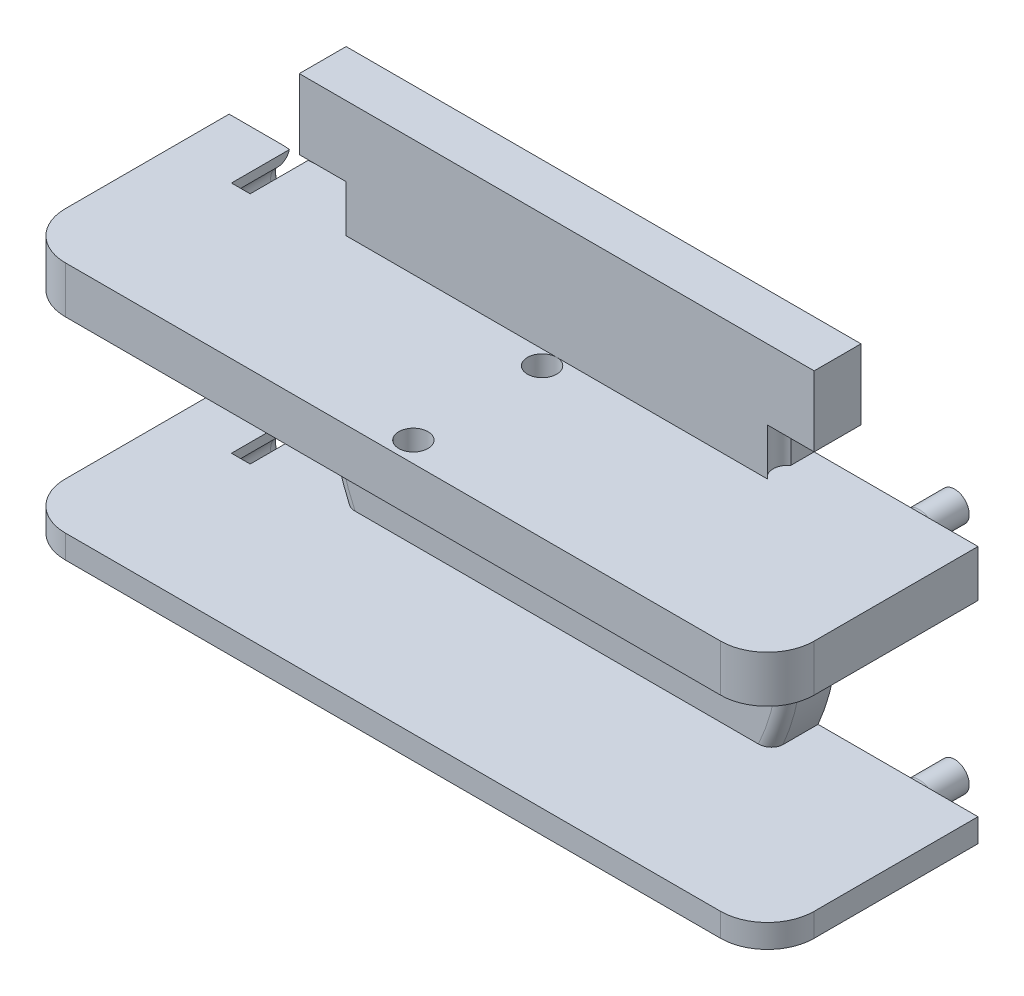
SolidWorks part; units mm, degrees
material "UNOBTANIUM"
ref_plane "Top Plane" through (0, 0, 0) normal (0, 0, 1) x (1, 0, 0)
ref_plane "Right Plane" through (0, 0, 0) normal (0, 1, 0) x (1, 0, 0)
ref_plane "Front Plane" through (0, 0, 0) normal (1, 0, 0) x (0, 0, -1)
ref_axis "x-axis" through (-17.6, 0, 0) along (1, 0, 0)
ref_axis "y-axis" through (0, -9.7375, 0) along (0, 1, 0)
ref_axis "z-axis" through (0, 0, 8.775) along (0, 0, -1)
sketch "Sketch1" plane through (0, 0, 0) normal (0, 0, 1) x (1, 0, 0)
  line L0 (-11, 6) -> (-11, 11)
  line L1 (-11, -6) -> (11, -6)
  line L2 (-11, -6) -> (-11, 6)
  line L3 (-11, 6) -> (11, 6) construction
  line L4 (11, -6) -> (11, 6)
  line L5 (-11, -6) -> (11, 6) construction
  line L6 (-11, 6) -> (11, -6) construction
  line L7 (-11, 11) -> (11, 11)
  line L8 (11, 11) -> (11, 6)
  circle A0 centre (0, 0) radius 9.25 construction
  point P0 (0, 0)
  dimension "D1" = 18.5
  dimension "D2" = 22
  dimension "D3" = 12
  dimension "D4" = 5
extrude "Boss-Extrude1" add sketch "Sketch1" along normal blind 2
sketch "Sketch2" plane through (0, 0, 2) normal (0, 0, -1) x (-1, 0, 0)
  circle A0 centre (0, 0) radius 1.575
  dimension "D1" = 3.15
extrude "Boss-Extrude2" add sketch "Sketch2" along normal blind 4 separate body
sketch "Sketch3" plane through (0, 0, 0) normal (0, 0, -1) x (-1, 0, 0)
  line L0 (11, -6) -> (-11, 6) construction
  circle A0 centre (0, 0) radius 1.8
  dimension "D1" = 3.6
extrude "Boss-Extrude3" add sketch "Sketch3" along normal blind 0.75
sketch "Sketch4" plane through (0, 0, 0) normal (0, 0, -1) x (-1, 0, 0)
  line L0 (11, -6) -> (-11, -6) construction
  line L1 (11, 11) -> (9, 11)
  line L2 (11, 11) -> (11, -6)
  line L3 (11, -6) -> (9, -6)
  line L4 (9, 11) -> (9, -6)
  line L5 (0, -6) -> (0, 11) construction
  line L7 (-9, 11) -> (-9, -6)
  line L8 (-11, -6) -> (-9, -6)
  line L9 (-11, 11) -> (-11, -6)
  line L10 (-11, 11) -> (-9, 11)
  line L11 (11, 11) -> (-11, 11) construction
  dimension "D1" = 2
extrude "Boss-Extrude4" add sketch "Sketch4" along normal blind 0.001
sketch "Sketch5" plane through (0, 0, 0) normal (0, 0, -1) x (-1, 0, 0)
  line L0 (-9, -6) -> (-9, 11) construction
  line L1 (9, 11) -> (-9, 11)
  line L2 (9, 11) -> (9, 9)
  line L3 (9, 9) -> (-9, 9)
  line L4 (-9, 11) -> (-9, 9)
  dimension "D1" = 2
extrude "Boss-Extrude5" add sketch "Sketch5" along normal up to surface (0.001 mm away) up to face at (-10, 2.5, -0.001)
sketch "Sketch6" plane through (11, 0, 0) normal (1, 0, 0) x (0, 0, -1)
  line L0 (-2, -6) -> (-2, 11) construction
  line L1 (0.001, -6) -> (-2, -6)
  line L2 (0.001, -6) -> (0.001, -4)
  line L3 (0.001, -4) -> (-2, -4)
  line L4 (-2, -6) -> (-2, -4)
  line L6 (0.001, 11) -> (0.001, -6) construction
  line L7 (-2, 6) -> (0.001, 6)
  line L8 (-2, 6) -> (-2, 4)
  line L9 (-2, 4) -> (0.001, 4)
  line L10 (0.001, 6) -> (0.001, 4)
  dimension "D1" = 2
extrude "Boss-Extrude6" add sketch "Sketch6" along normal blind 5
mirror "Mirror1" about plane through (0, 0, 0) normal (1, 0, 0) of "Boss-Extrude6"
sketch "Sketch7" plane through (0, 0, -0.001) normal (0, 0, -1) x (-1, 0, 0)
  line L0 (-9, -6) -> (-9, 9) construction
  line L1 (-9, 0) -> (-9, 9)
  line L2 (-9, 9) -> (0, 9)
  line L3 (-9, 0) -> (-9, -6)
  line L4 (-9, -6) -> (-6.7082, -6)
  line L5 (11, -6) -> (-11, -6) construction
  arc A0 (0, 9) -> (-6.7082, -6) centre (0, 0) ccw
  line M18 (-9, -6) -> (-9, 9)
  line M19 (-9, 9) -> (9, 9)
extrude "Boss-Extrude7" add sketch "Sketch7" against normal up to surface (0.001 mm away) contours A0 L4 M18 | A0 M19 M18 region at (8.3306, -4.5409, -0.001) region at (6.9897, 6.9897, -0.001) up to face at (1.8, 0, 0)
sketch "Sketch8" plane through (0, 0, -0.001) normal (0, 0, -1) x (-1, 0, 0)
  line L0 (-11, 4) -> (-9.1652, 4)
  line L1 (-11, 4) -> (-11, -4)
  line L2 (-11, -4) -> (-9.1652, -4)
  arc A1 (-9.1652, 4) -> (-9.1652, -4) centre (0, 0) ccw
  dimension "D1" = 10
extrude "Cut-Extrude1" cut sketch "Sketch8" against normal through all
sketch "Sketch9" plane through (0, 0, -0.001) normal (0, 0, -1) x (-1, 0, 0)
  line L0 (-16, -4) -> (-9.1652, -4) construction
  line L1 (-8.0623, 4) -> (-11, 4)
  line L2 (-8.0623, 4) -> (-8.0623, -4)
  line L3 (-8.0623, -4) -> (-11, -4)
  line L4 (-11, 4) -> (-11, -4)
  line L5 (-11, -6) -> (-11, 6) construction
  arc A0 (0, 9) -> (-6.7082, -6) centre (0, 0) ccw construction
  arc A1 (0, 9) -> (-6.7082, -6) centre (0, 0) ccw construction
extrude "Cut-Extrude2" cut sketch "Sketch9" against normal up to surface (0.001 mm away) up to face at (1.8, 0, 0)
mirror "Mirror2" about plane through (0, 0, 0) normal (1, 0, 0) of "Cut-Extrude2", "Boss-Extrude7", "Cut-Extrude1"
sketch "Sketch21" plane through (0, 0, -0.001) normal (0, 0, -1) x (-1, 0, 0)
  circle A0 centre (0, 0) radius 9.75
  circle A1 centre (0, 0) radius 9 construction
  circle A2 centre (0, 0) radius 1.8 construction
  circle A3 centre (0, 0) radius 1.8
  dimension "D1" = 0.75
extrude "Cut-Extrude11" cut sketch "Sketch21" against normal up to surface (0.001 mm away) up to face at (0, -0.7091, 0)
sketch "Sketch10" plane through (0, 0, 2) normal (0, 0, 1) x (1, 0, 0)
  line L0 (-16, -4) -> (-16, -6) construction
  line L1 (16, -6) -> (-16, -6)
  line L2 (16, -6) -> (16, -4)
  line L3 (16, -4) -> (-16, -4)
  line L4 (-16, -6) -> (-16, -4)
  line L5 (-16, -4) -> (-9.1652, -4) construction
  line L7 (-16, 6) -> (16, 6)
  line L8 (-16, 6) -> (-16, 4)
  line L9 (-16, 4) -> (16, 4)
  line L10 (16, 6) -> (16, 4)
extrude "Boss-Extrude8" add sketch "Sketch10" along normal blind 7
fillet "Fillet1" radius 0.5 2 edges at (10, 0, 2) (-10, 0, 2)
sketch "Sketch11" plane through (0, 0, -0.001) normal (0, 0, -1) x (-1, 0, 0)
  line L0 (-16, -5) -> (-13, -5) construction
  line L1 (-16, -6) -> (-16, -4) construction
  circle A0 centre (-13, -5) radius 0.625
  dimension "D1" = 1.25
  dimension "D2" = 3
extrude "Boss-Extrude9" add sketch "Sketch11" along normal blind 2
sketch "Sketch14" plane through (0, 0, -0.001) normal (0, 0, -1) x (-1, 0, 0)
  line L1 (11, 6) -> (9, 6)
  line L2 (11, 6) -> (11, 8)
  line L3 (11, 8) -> (9, 8)
  line L4 (9, 6) -> (9, 8)
  line L5 (-11, 6) -> (-9, 6)
  line L6 (-11, 6) -> (-11, 8)
  line L7 (-11, 8) -> (-9, 8)
  line L8 (-9, 6) -> (-9, 8)
  dimension "D1" = 18
  dimension "D2" = 2
extrude "Cut-Extrude5" cut sketch "Sketch14" against normal through all
sketch "Sketch12" plane through (0, 0, -0.001) normal (0, 0, -1) x (-1, 0, 0)
  line L0 (-16, -5) -> (-13, -5) construction
  line L1 (-16, -6) -> (-16, -4) construction
  line L3 (16, -5) -> (13, -5) construction
  line L4 (16, -6) -> (16, -4) construction
  circle A0 centre (13, -5) radius 0.725
  circle A1 centre (-13, -5) radius 0.625 construction
  circle A2 centre (-13, -5) radius 0.625 construction
  dimension "D1" = 1.45
  dimension "D2" = 1.25
extrude "Cut-Extrude3" cut sketch "Sketch12" against normal blind 2.5
sketch "Sketch16" plane through (0, 6, 0) normal (0, 1, 0) x (1, 0, 0)
  line L0 (-9, -2) -> (-9, 0.001) construction
  line L1 (-9, -1) -> (-9, -2)
  arc A1 (-9, -1) -> (-9, -2) centre (-9.375, -1.5) cw
  dimension "D1" = 0.25
  dimension "D2" = 1
extrude "Cut-Extrude6" cut sketch "Sketch16" along normal blind 2
mirror "Mirror3" about plane through (0, 0, 0) normal (0, 1, 0) of "Boss-Extrude9", "Cut-Extrude3"
mirror "Mirror4" about plane through (0, 0, 0) normal (1, 0, 0) of "Cut-Extrude6"
fillet "Fillet2" radius 0.5 2 edges at (12.375, 5, -0.001) (13.625, -5, -0.001)
fillet "Fillet3" radius 0.5 2 edges at (-13.725, 5, -0.001) (-13.725, -5, -0.001)
fillet "Fillet4" radius 2 4 edges at (16, -5, 9) (16, 5, 9) (-16, -5, 9) (-16, 5, 9)
sketch "Sketch17" plane through (0, -6, 0) normal (0, -1, 0) x (1, 0, 0)
  line L0 (-16, 7) -> (-16, -0.001) construction
  line L1 (-14, 9) -> (14, 9) construction
  line L2 (16, 7) -> (16, -0.001) construction
  line L3 (-16, 7) -> (-16, -0.001)
  line L4 (-14, 9) -> (14, 9)
  line L5 (16, 7) -> (16, -0.001)
  line L6 (14.5, 7) -> (14.5, -0.001)
  line L8 (-14, 7.5) -> (14, 7.5)
  line L9 (-14.5, 7) -> (-14.5, -0.001)
  line L10 (14.5, -0.001) -> (16, -0.001)
  line L11 (-14.5, -0.001) -> (-16, -0.001)
  arc A0 (-14, 9) -> (-16, 7) centre (-14, 7) ccw construction
  arc A1 (16, 7) -> (14, 9) centre (14, 7) ccw construction
  arc A2 (-14, 9) -> (-16, 7) centre (-14, 7) ccw
  arc A3 (16, 7) -> (14, 9) centre (14, 7) ccw
  arc A4 (14.5, 7) -> (14, 7.5) centre (14, 7) ccw
  arc A5 (-14, 7.5) -> (-14.5, 7) centre (-14, 7) ccw
  dimension "D1" = 1.5
extrude "Cut-Extrude7" cut sketch "Sketch17" against normal blind 1 and the other way through all
sketch "Sketch19" plane through (0, 6, 0) normal (0, 1, 0) x (1, 0, 0)
  line L0 (9, -2) -> (-9, -2) construction
  line L1 (0, -2.625) -> (0, -2) construction
  line L2 (9, -2) -> (-9, -2) construction
  circle A0 centre (0, -2.625) radius 0.625
  circle A1 centre (0, -8.125) radius 0.625
  point P4 (0, -2)
  dimension "D1" = 1.25
  dimension "D2" = 5.5
extrude "Cut-Extrude9" cut sketch "Sketch19" against normal up to surface (2 mm away) up to face at (-0.0266, 4, 1.9999)
sketch "Sketch20" plane through (0, 0, -0.001) normal (0, 0, -1) x (-1, 0, 0)
  line L0 (-9, 8) -> (-11, 8) construction
  line L1 (-11, 11) -> (-9, 11)
  line L2 (-11, 11) -> (-11, 8)
  line L3 (-11, 8) -> (-9, 8)
  line L4 (-9, 11) -> (-9, 8)
  line L5 (11, 11) -> (-11, 11) construction
  line L6 (11, 8) -> (9, 8)
  line L7 (11, 8) -> (11, 11)
  line L8 (11, 11) -> (9, 11)
  line L9 (9, 8) -> (9, 11)
  dimension "D1" = 2
combine bodies "Combine2" operation type subtract main body 122 bodies to subtract 102
sketch "Sketch23" plane through (0, 0, -0.001) normal (0, 0, -1) x (-1, 0, 0)
  line L0 (13, -6) -> (13, -4) construction
  line L1 (12.2925, -6) -> (13.7075, -6) construction
  line L2 (13.7075, -4) -> (12.2925, -4) construction
  line L3 (12.6, -6) -> (12.6, -4)
  line L4 (13.4, -6) -> (13.4, -4)
  arc A0 (12.6, -6) -> (13.4, -6) centre (13, -6) ccw
  arc A1 (13.4, -4) -> (12.6, -4) centre (13, -4) ccw
  point P6 (13, -5)
  dimension "D1" = 0.8
extrude "Cut-Extrude12" cut sketch "Sketch23" against normal up to surface (2.5 mm away) up to face at (-13.725, -5, 2.499)
mirror "Mirror5" about plane through (0, 0, 0) normal (0, 1, 0) of "Cut-Extrude12"
equation "\"D1@Sketch12\"=\"D2@Sketch12\"+.2"
